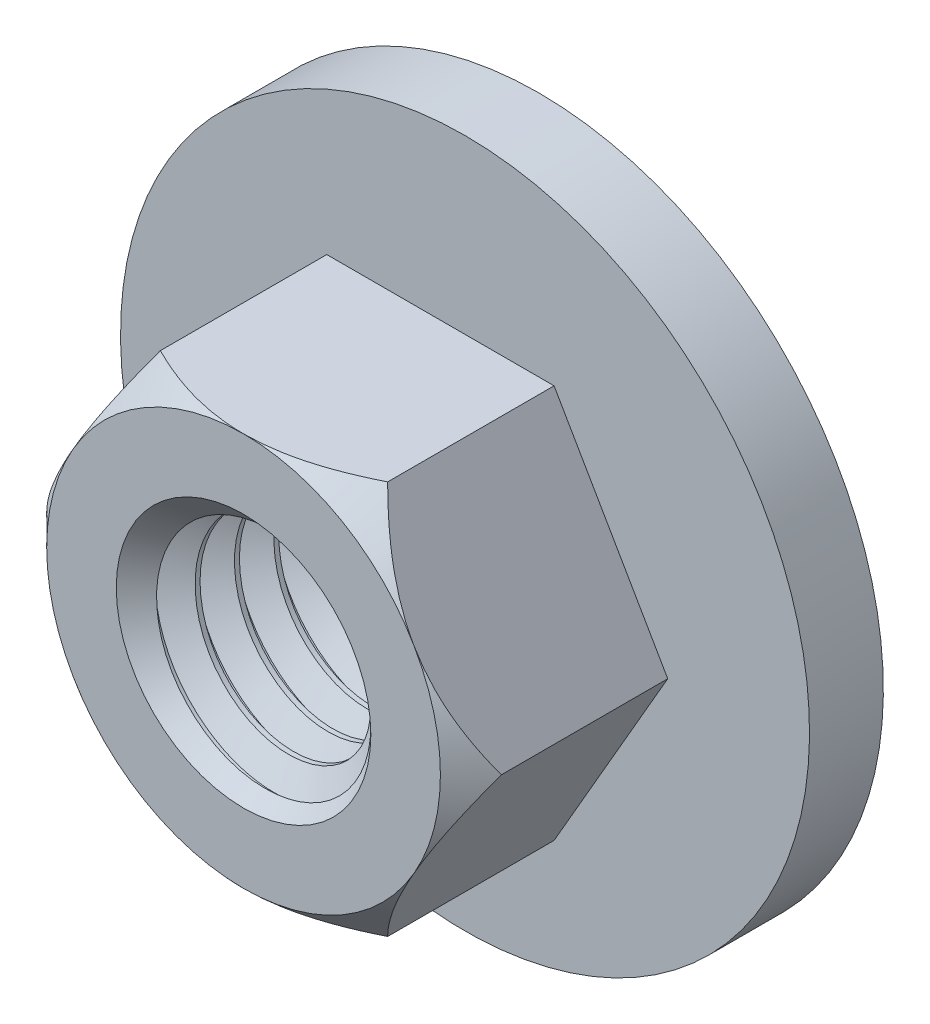
SolidWorks part; units mm, degrees
ref_plane "Front Plane" through (0, 0, 0) normal (0, 0, 1) x (1, 0, 0)
ref_plane "Top Plane" through (0, 0, 0) normal (0, 1, 0) x (1, 0, 0)
ref_plane "Right Plane" through (0, 0, 0) normal (1, 0, 0) x (0, 0, -1)
sketch "Sketch1" plane through (0, 0, 0) normal (1, 0, 0) x (0, 0, -1)
  line L0 (3, 0) -> (-3, 0) construction
  line L1 (-3, 0) -> (-3, 4) construction
  line L2 (-3, 4) -> (1, 4) construction
  line L3 (1, 4) -> (1, 3.25) construction
  line L4 (1, 3.25) -> (1.5, 3.25) construction
  line L5 (1.5, 3.25) -> (1.5, 7) construction
  line L6 (1.5, 7) -> (3, 7) construction
  line L7 (3, 7) -> (3, 0) construction
  line L8 (3, 2.5) -> (-3, 2.5) construction
  line L9 (1, 3.25) -> (1, 2.5) construction
  line L10 (-3.75, 2.5866) -> (-3.35, 1.8938) construction
  line L11 (-3.35, 1.8938) -> (-2.95, 2.5866) construction
  line L12 (-2.95, 2.5866) -> (-3.75, 2.5866) construction
  line L13 (-3.35, 2.5866) -> (-3.35, 2.5) construction
  line L14 (-3.35, 1.8938) -> (-3.35, 1.9804) construction
  line L15 (-3.4, 1.9804) -> (-3.3, 1.9804) construction
  line L16 (-3.7, 2.5) -> (-3, 2.5) construction
  line L17 (-3.725, 2.5433) -> (-2.975, 2.5433) construction
  point P4 (0, 0)
  point P23 (-3.35, 1.9804)
  point P25 (-3.35, 2.5)
  point P29 (-3.35, 2.5433)
  dimension "Flange Thickness" = 1.5
  dimension "Flange Diameter" = 14
  dimension "Width" = 8
  dimension "Height" = 6
  dimension "D2" = 0.5
  dimension "Thread Size" = 5
  dimension "Thread Pitch" = 0.8
  dimension "D1" = 0.1
sketch "Sketch2" plane through (0, 0, 0) normal (1, 0, 0) x (0, 0, -1)
  line L0 (-3, 2.5) -> (-3, 4)
  line L1 (-3, 4) -> (1, 4)
  line L2 (1, 4) -> (1, 3.25)
  line L3 (1, 3.25) -> (1.5, 3.25)
  line L4 (1.5, 3.25) -> (1.5, 7)
  line L5 (1.5, 7) -> (3, 7)
  line L6 (3, 7) -> (3, 2.5)
  line L7 (3, 2.5) -> (-3, 2.5)
revolve "Revolve1" add sketch "Sketch2" angle 360 about L0
sketch "Sketch4" plane through (0, 0, 3) normal (0, 0, 1) x (1, 0, 0)
  line L1 (4.6188, 0) -> (2.3094, 4)
  line L2 (2.3094, 4) -> (-2.3094, 4)
  line L3 (-2.3094, 4) -> (-4.6188, 0)
  line L4 (-4.6188, 0) -> (-2.3094, -4)
  line L5 (-2.3094, -4) -> (2.3094, -4)
  line L6 (2.3094, -4) -> (4.6188, 0)
  circle A0 centre (0, 0) radius 4 construction
  circle A1 centre (0, 0) radius 2.5
  point P1 (0, 4)
  point P13 (0, -2.5)
  point P14 (2.5, 0)
  point P15 (-2.5, 0)
  point P16 (0, 2.5)
extrude "Boss-Extrude1" add sketch "Sketch4" against normal up to vertex (4 mm away) up to point (0, 4, -1)
sketch "Sketch5" plane through (0, 0, 3) normal (0, 0, 1) x (1, 0, 0)
  circle A0 centre (0, 0) radius 4
extrude "Cut-Extrude1" cut sketch "Sketch5" against normal blind 10 draft 45 flip side to cut
fillet "Fillet1" radius 0.5 1 edges at (0, 3.25, -1)
sketch "Sketch7" plane through (0, 0, 3) normal (0, 0, 1) x (1, 0, 0)
  circle A0 centre (0, 0) radius 2.5
curve "Helix/Spiral1" pitch 0.8 height 6.8 radius 2.5 centre (0, 0, 3) axis (0, 0, -1) start towards (0, 1, 0)
sketch "Sketch8" plane through (0, 0, 0) normal (1, 0, 0) x (0, 0, -1)
  line L0 (-3.725, 2.5433) -> (-2.975, 2.5433)
  line L1 (-2.975, 2.5433) -> (-3.3, 1.9804)
  line L2 (-3.3, 1.9804) -> (-3.4, 1.9804)
  line L3 (-3.4, 1.9804) -> (-3.725, 2.5433)
sweep "Sweep1" add profiles "Sketch8" path "Helix/Spiral1"
sketch "Sketch9" plane through (0, 0, 3) normal (0, 0, 1) x (1, 0, 0)
  line L0 (0, 0) -> (0, 1.9804) construction
  line L1 (0, 0) -> (0, -1.9804) construction
  circle A0 centre (0, 0) radius 2.5866
  point P3 (0, -1.9804)
extrude "Cut-Extrude3" cut sketch "Sketch9" along normal through all and the other way through all draft 45
sketch "Sketch10" plane through (0, 0, -3) normal (0, 0, -1) x (-1, 0, 0)
  circle A0 centre (0, 0) radius 2.5866
extrude "Cut-Extrude4" cut sketch "Sketch10" along normal through all and the other way through all draft 45
equation "\"D2@Sketch1\"= \"Height@Sketch1\" / 12"
equation "\"D1@Sketch1\" = \"Thread Pitch@Sketch1\" / 8"
equation "\"D4@Helix/Spiral1\" = \"Thread Pitch@Sketch1\""
equation "\"D3@Helix/Spiral1\"= \"Thread Pitch@Sketch1\" + \"Height@Sketch1\""
